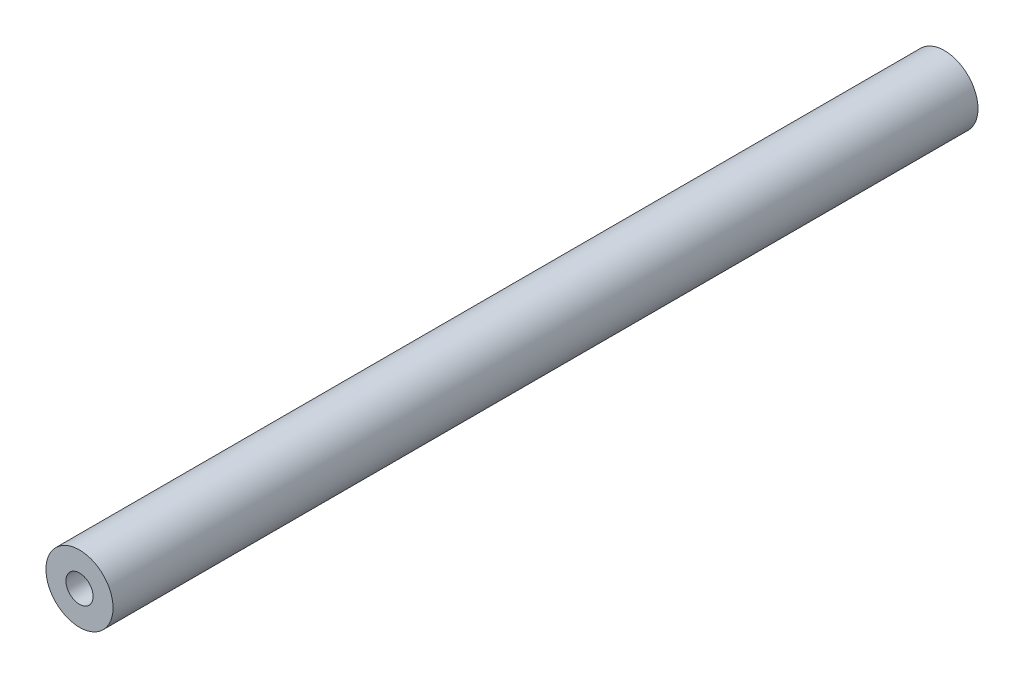
SolidWorks part; units mm, degrees
material "6061-T6 (SS)"
ref_plane "Front Plane" through (0, 0, 0) normal (0, 0, 1) x (1, 0, 0)
ref_plane "Top Plane" through (0, 0, 0) normal (0, 1, 0) x (1, 0, 0)
ref_plane "Right Plane" through (0, 0, 0) normal (1, 0, 0) x (0, 0, -1)
sketch "Sketch1" plane through (0, 0, 0) normal (0, 0, 1) x (1, 0, 0)
  circle A0 centre (0, 0) radius 6.4
  dimension "D1" = 12.8
extrude "Boss-Extrude1" add sketch "Sketch1" along normal blind 165
hole_wizard "#6 (0.204) Diameter Hole1" positions "Sketch2" profile "Sketch3" hole size "#6" standard "ANSI Inch"
sketch "Sketch2" plane through (0, 0, 0) normal (0, 0, -1) x (-1, 0, 0)
  point P0 (0, 0)
sketch "Sketch3" plane through (0, 0, 0) normal (1, 0, 0) x (0, 1, 0)
  line L0 (0, 0) -> (0, 31.5567)
  line L1 (0, 31.5567) -> (2.5908, 30)
  line L2 (2.5908, 30) -> (2.5908, 0)
  line L5 (2.5908, 0) -> (0, 0)
  line L10 (0, 31.5567) -> (-2.5908, 30) construction
  line L11 (0, -6.35) -> (0, 107.95) construction
  dimension "Hole Dia." = 5.1816
  dimension "Hole Depth" = 30
  dimension "Drill Angle" = 118
hole_wizard "#6 (0.204) Diameter Hole2" positions "Sketch4" profile "Sketch5" hole size "#6" standard "ANSI Inch"
sketch "Sketch4" plane through (0, 0, 165) normal (0, 0, 1) x (1, 0, 0)
  point P0 (0, 0)
sketch "Sketch5" plane through (0, 0, 165) normal (1, 0, 0) x (0, -1, 0)
  line L0 (0, 0) -> (0, 31.5567)
  line L1 (0, 31.5567) -> (2.5908, 30)
  line L2 (2.5908, 30) -> (2.5908, 0)
  line L5 (2.5908, 0) -> (0, 0)
  line L10 (0, 31.5567) -> (-2.5908, 30) construction
  line L11 (0, -6.35) -> (0, 107.95) construction
  dimension "Hole Dia." = 5.1816
  dimension "Hole Depth" = 30
  dimension "Drill Angle" = 118
